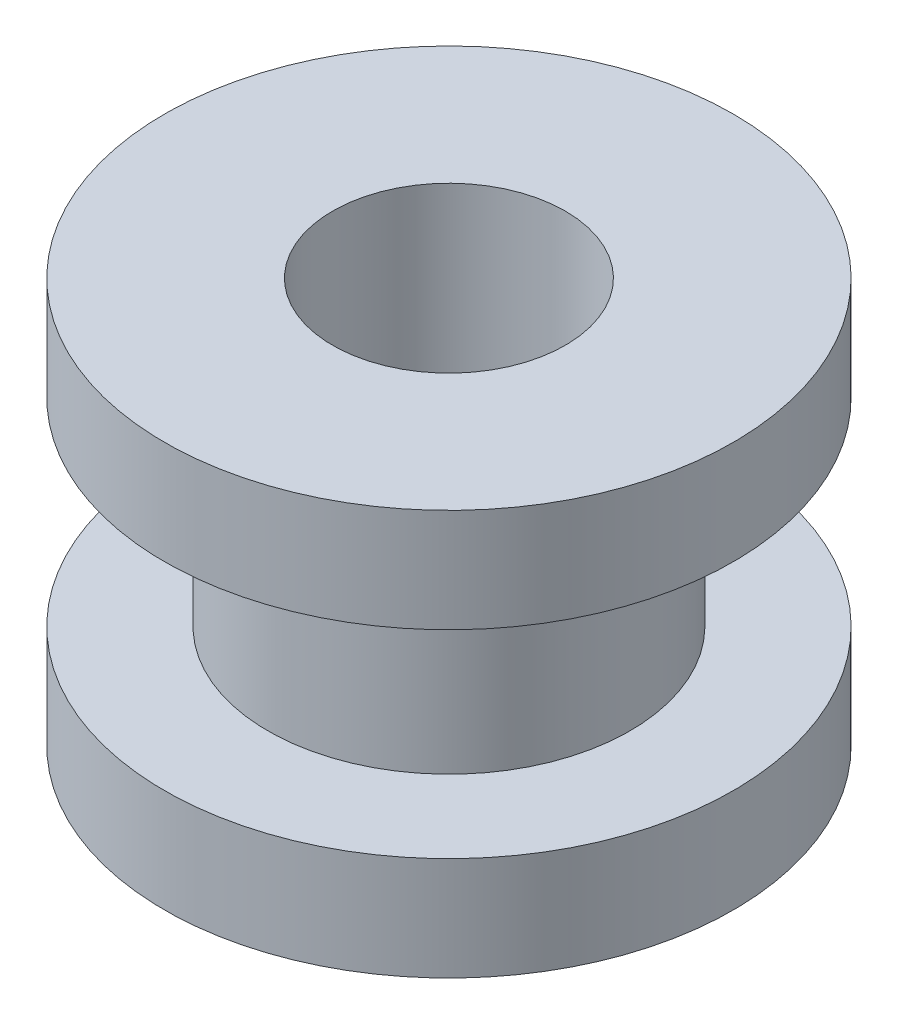
SolidWorks part; units mm, degrees
ref_plane "前视基准面" through (0, 0, 0) normal (0, 0, 1) x (1, 0, 0)
ref_plane "上视基准面" through (0, 0, 0) normal (0, 1, 0) x (1, 0, 0)
ref_plane "右视基准面" through (0, 0, 0) normal (1, 0, 0) x (0, 0, -1)
other "Configuration Table"
sketch "草图1" plane through (0, 0, 0) normal (0, 0, 1) x (1, 0, 0)
  line L0 (0, 0) -> (0, 7.2151) construction
  line L1 (-1.35, 2.35) -> (-3.3, 2.35)
  line L2 (-3.3, 2.35) -> (-3.3, 1.15)
  line L3 (-3.3, 1.15) -> (-2.1, 1.15)
  line L4 (-2.1, 1.15) -> (-2.1, -1.15)
  line L5 (-2.1, -1.15) -> (-3.3, -1.15)
  line L6 (-3.3, -1.15) -> (-3.3, -2.35)
  line L7 (-3.3, -2.35) -> (-1.35, -2.35)
  line L10 (-1.35, -2.35) -> (-1.35, 2.35)
  point P3 (-1.35, 0)
  dimension "D1" = 1.2
  dimension "D2" = 2.7
  dimension "D3" = 6.6
  dimension "D4" = 4.2
  dimension "D5" = 2.3
revolve "旋转1" add sketch "草图1" angle 360 about L0
ref_axis "基准轴1" through (0, -21.8591, 0) along (0, 1, 0)
